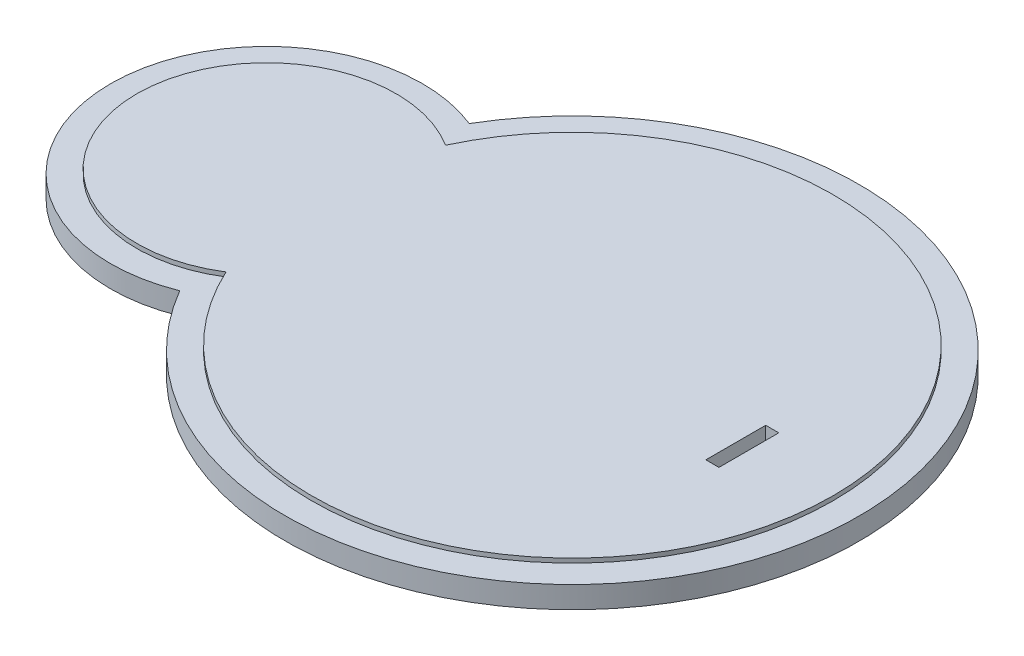
SolidWorks part; units mm, degrees
ref_plane "Front Plane" through (0, 0, 0) normal (0, 0, 1) x (1, 0, 0)
ref_plane "Top Plane" through (0, 0, 0) normal (0, 1, 0) x (1, 0, 0)
ref_plane "Right Plane" through (0, 0, 0) normal (1, 0, 0) x (0, 0, -1)
sketch "Sketch1" plane through (0, 0, 0) normal (0, 1, 0) x (1, 0, 0)
  arc A0 (-54.1571, -25.1216) -> (-54.1571, 25.1216) centre (0, 0) ccw
  arc A1 (-54.1571, 25.1216) -> (-54.1571, -25.1216) centre (-70, 0) ccw
  arc A2 (-56.7286, -33.1415) -> (-56.7286, 33.1415) centre (0, 0) ccw
  arc A3 (-56.7286, 33.1415) -> (-56.7286, -33.1415) centre (-70, 0) ccw
  point P1 (0, 0)
  dimension "D1" = 59.7
  dimension "D2" = 65.7
  dimension "D3" = 29.7
  dimension "D4" = 35.7
  dimension "D5" = 70
extrude "Boss-Extrude1" add sketch "Sketch1" along normal blind 6 contours A1 A0
extrude "Boss-Extrude2" add sketch "Sketch1<3>" along normal blind 5
sketch "Sketch1<3>" plane through (0, 0, 0) normal (0, 1, 0) x (1, 0, 0) same geometry as "Sketch1"
sketch "Sketch2" plane through (0, 6, 0) normal (0, 1, 0) x (1, 0, 0)
  line L1 (38.0081, 6.254) -> (41.0081, 6.254)
  line L2 (38.0081, 6.254) -> (38.0081, -7.446)
  line L3 (38.0081, -7.446) -> (41.0081, -7.446)
  line L4 (41.0081, 6.254) -> (41.0081, -7.446)
  point P4 (0, 0)
  dimension "D1" = 13.7
  dimension "D2" = 3
extrude "Cut-Extrude1" cut sketch "Sketch2" against normal through all
